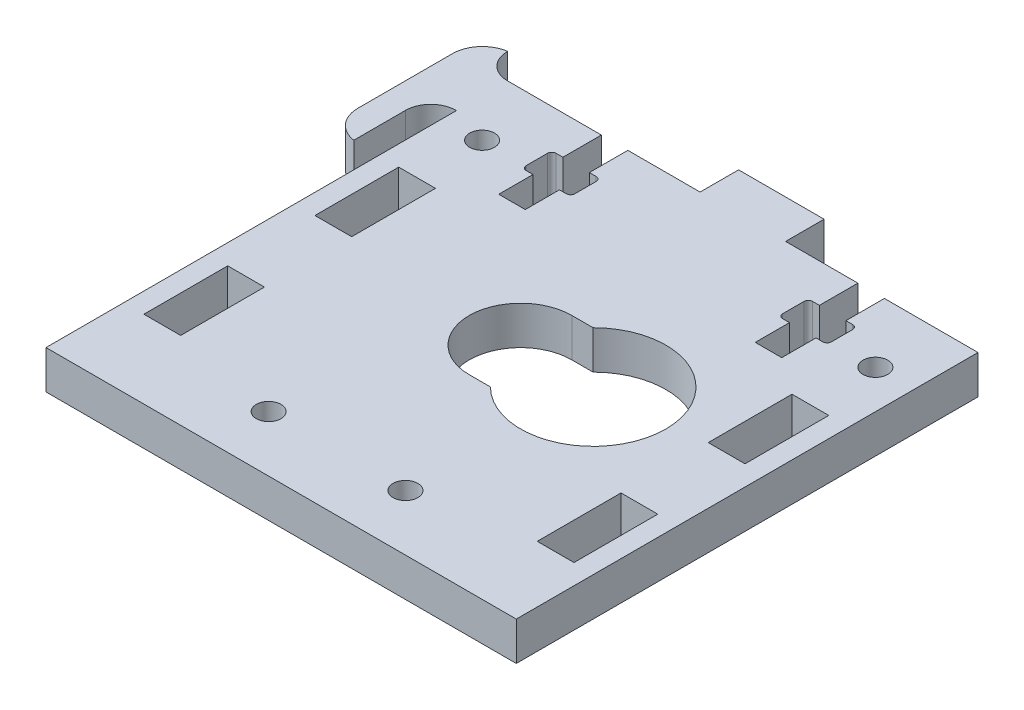
SolidWorks part; units mm, degrees
ref_plane "Front Plane" through (0, 0, 0) normal (0, 0, 1) x (1, 0, 0)
ref_plane "Top Plane" through (0, 0, 0) normal (0, 1, 0) x (1, 0, 0)
ref_plane "Right Plane" through (0, 0, 0) normal (1, 0, 0) x (0, 0, -1)
sketch "Sketch1" plane through (0, 0, 0) normal (0, 1, 0) x (1, 0, 0)
  line L1 (-27.5, 27) -> (27.5, 27)
  line L2 (-27.5, 27) -> (-27.5, -27)
  line L3 (-27.5, -27) -> (27.5, -27)
  line L4 (27.5, 27) -> (27.5, -27)
  line L5 (-27.5, 27) -> (27.5, -27) construction
  line L6 (-27.5, -27) -> (27.5, 27) construction
  point P0 (0, 0)
  dimension "D1" = 55
  dimension "D2" = 54
extrude "MainShape" add sketch "Sketch1" along normal blind 4.5
sketch "Sketch2" plane through (0, 4.5, 0) normal (0, 1, 0) x (1, 0, 0)
  line L0 (0, -27) -> (0, 27) construction
  line L1 (-27.5, -27) -> (27.5, -27) construction
  line L2 (27.5, 27) -> (-27.5, 27) construction
  line L4 (-5, 31.5) -> (5, 31.5)
  line L5 (-5, 31.5) -> (-5, 22.5)
  line L6 (-5, 22.5) -> (5, 22.5)
  line L7 (5, 31.5) -> (5, 22.5)
  line L8 (-5, 31.5) -> (5, 22.5) construction
  line L9 (-5, 22.5) -> (5, 31.5) construction
  dimension "D1" = 10
  dimension "D2" = 4.5
extrude "Tab1" add sketch "Sketch2" against normal through all
sketch "Sketch4" plane through (0, 4.5, 0) normal (0, 1, 0) x (1, 0, 0)
  line L0 (0, 31.5) -> (0, -27) construction
  line L1 (5, 31.5) -> (-5, 31.5) construction
  line L2 (-27.5, -27) -> (27.5, -27) construction
  line L3 (-15, 27) -> (-15, 15) construction
  line L4 (-5, 27) -> (-27.5, 27) construction
  line L5 (-13.45, 15) -> (-16.55, 15) construction
  line L6 (-16.55, 15) -> (-16.55, 27) construction
  line L7 (-13.45, 15) -> (-16.55, 15)
  line L8 (-16.55, 15) -> (-16.55, 19)
  line L9 (-16.55, 19) -> (-17.35, 19)
  line L10 (-17.85, 19.5) -> (-17.85, 22)
  line L11 (-17.35, 22.5) -> (-16.55, 22.5)
  line L12 (-16.55, 22.5) -> (-16.55, 27)
  line L13 (-16.55, 27) -> (-13.45, 27)
  line L14 (-13.45, 15) -> (-13.45, 27) construction
  line L15 (-13.45, 22.5) -> (-13.45, 27)
  line L16 (-12.65, 22.5) -> (-13.45, 22.5)
  line L17 (-12.15, 19.5) -> (-12.15, 22)
  line L18 (-13.45, 19) -> (-12.65, 19)
  line L19 (-13.45, 15) -> (-13.45, 19)
  line L20 (13.45, 15) -> (13.45, 27) construction
  line L21 (16.55, 15) -> (16.55, 27) construction
  line L22 (13.45, 15) -> (16.55, 15) construction
  line L23 (15, 27) -> (15, 15) construction
  line L24 (13.45, 15) -> (13.45, 19)
  line L25 (13.45, 19) -> (12.65, 19)
  line L26 (12.15, 19.5) -> (12.15, 22)
  line L27 (12.65, 22.5) -> (13.45, 22.5)
  line L28 (13.45, 22.5) -> (13.45, 27)
  line L29 (16.55, 27) -> (13.45, 27)
  line L30 (16.55, 22.5) -> (16.55, 27)
  line L31 (17.35, 22.5) -> (16.55, 22.5)
  line L32 (17.85, 19.5) -> (17.85, 22)
  line L33 (16.55, 19) -> (17.35, 19)
  line L34 (16.55, 15) -> (16.55, 19)
  line L35 (13.45, 15) -> (16.55, 15)
  arc A0 (-17.35, 19) -> (-17.85, 19.5) centre (-17.35, 19.5) cw
  arc A1 (-12.15, 19.5) -> (-12.65, 19) centre (-12.65, 19.5) cw
  arc A2 (-12.65, 22.5) -> (-12.15, 22) centre (-12.65, 22) cw
  arc A3 (-17.85, 22) -> (-17.35, 22.5) centre (-17.35, 22) cw
  arc A4 (17.85, 22) -> (17.35, 22.5) centre (17.35, 22) ccw
  arc A5 (12.65, 22.5) -> (12.15, 22) centre (12.65, 22) ccw
  arc A6 (12.15, 19.5) -> (12.65, 19) centre (12.65, 19.5) ccw
  arc A7 (17.35, 19) -> (17.85, 19.5) centre (17.35, 19.5) ccw
  point P24 (-17.85, 19)
  point P27 (-12.15, 19)
  point P30 (-12.15, 22.5)
  point P33 (-17.85, 22.5)
  point P56 (17.85, 22.5)
  point P57 (12.15, 22.5)
  point P58 (12.15, 19)
  point P59 (17.85, 19)
  dimension "D7" = 0.5
  dimension "D1" = 12
  dimension "D2" = 1.55
  dimension "D3" = 3.5
  dimension "D4" = 2.85
  dimension "D5" = 8
  dimension "D6" = 15
extrude "Cut-Extrude2" cut sketch "Sketch4" against normal through all
sketch "Sketch5" plane through (0, 4.5, 0) normal (0, 1, 0) x (1, 0, 0)
  line L0 (0, -27) -> (0, 31.5) construction
  line L1 (-27.5, -27) -> (27.5, -27) construction
  line L2 (5, 31.5) -> (-5, 31.5) construction
  line L3 (23, 27) -> (23, -27) construction
  line L4 (27.5, 27) -> (16.55, 27) construction
  line L5 (-23, 27) -> (-23, -27) construction
  line L6 (20.85, 11.9) -> (25.15, 11.9)
  line L7 (20.85, 11.9) -> (20.85, 2.1)
  line L8 (20.85, 2.1) -> (25.15, 2.1)
  line L9 (25.15, 11.9) -> (25.15, 2.1)
  line L10 (20.85, 11.9) -> (25.15, 2.1) construction
  line L11 (20.85, 2.1) -> (25.15, 11.9) construction
  line L12 (-20.85, 2.1) -> (-25.15, 11.9) construction
  line L13 (-20.85, 11.9) -> (-25.15, 2.1) construction
  line L14 (-25.15, 11.9) -> (-25.15, 2.1)
  line L15 (-20.85, 2.1) -> (-25.15, 2.1)
  line L16 (-20.85, 11.9) -> (-20.85, 2.1)
  line L17 (-20.85, 11.9) -> (-25.15, 11.9)
  line L18 (-27.5, -3) -> (27.5, -3) construction
  line L19 (-27.5, 27) -> (-27.5, -27) construction
  line L20 (27.5, -27) -> (27.5, 27) construction
  line L21 (-20.85, -17.9) -> (-25.15, -8.1) construction
  line L22 (-20.85, -8.1) -> (-25.15, -17.9) construction
  line L23 (20.85, -8.1) -> (25.15, -17.9) construction
  line L24 (20.85, -17.9) -> (25.15, -8.1) construction
  line L25 (-20.85, -17.9) -> (-25.15, -17.9)
  line L26 (-20.85, -17.9) -> (-20.85, -8.1)
  line L27 (-20.85, -8.1) -> (-25.15, -8.1)
  line L28 (-25.15, -17.9) -> (-25.15, -8.1)
  line L29 (25.15, -17.9) -> (25.15, -8.1)
  line L30 (20.85, -8.1) -> (25.15, -8.1)
  line L31 (20.85, -17.9) -> (20.85, -8.1)
  line L32 (20.85, -17.9) -> (25.15, -17.9)
  line L33 (-20.85, 11.9) -> (-25.15, 2.1) construction
  point P10 (23, 7)
  point P21 (-23, 7)
  point P36 (-23, -13)
  point P37 (23, -13)
  dimension "D1" = 23
  dimension "D2" = 9.8
  dimension "D3" = 4.3
  dimension "D4" = 20
  dimension "D5" = 20
extrude "Cut-Extrude3" cut sketch "Sketch5" against normal through all
sketch "Sketch6" plane through (0, 4.5, 0) normal (0, 1, 0) x (1, 0, 0)
  line L0 (0, -27) -> (0, 27) construction
  line L1 (5, 31.5) -> (-5, 31.5) construction
  line L3 (-27.5, 1) -> (27.5, 1) construction
  line L4 (-27.5, 27) -> (-27.5, -27) construction
  line L5 (27.5, -27) -> (27.5, 27) construction
  line L6 (27.5, 27) -> (16.55, 27) construction
  line L7 (-27.5, -27) -> (27.5, -27) construction
  line L9 (-27.5, 27) -> (27.5, 27) construction
  circle A0 centre (0, 1) radius 12
  point P4 (0, 31.5)
  dimension "D1" = 24
  dimension "D2" = 26
extrude "Cut-Extrude4" cut sketch "Sketch6" against normal through all
sketch "Sketch7" plane through (0, 4.5, 0) normal (0, 1, 0) x (1, 0, 0)
  line L0 (0, 1) -> (0, -27) construction
  line L3 (-27.5, -27) -> (27.5, -27) construction
  line L4 (8, -20.46) -> (-8, -20.46) construction
  circle A1 centre (-8, -20.46) radius 1.45
  circle A2 centre (8, -20.46) radius 1.45
  point P8 (0, -20.46)
  dimension "D1" = 2.9
  dimension "D3" = 21.46
extrude "Cut-Extrude5" [suppressed] cut sketch "Sketch7" against normal through all
sketch "Sketch8" plane through (0, 4.5, 0) normal (0, 1, 0) x (1, 0, 0)
  line L0 (-12, 1) -> (12, 1) construction
  line L1 (0, 1) -> (0, -20.46) construction
  line L2 (8, -20.46) -> (-8, -20.46) construction
  line L3 (0, -11) -> (0, 13) construction
  circle A0 centre (-8, -20.46) radius 1.45
  circle A1 centre (0, 1) radius 12 construction
  circle A2 centre (8, -20.46) radius 1.45
  dimension "D3" = 2.9
  dimension "D1" = 90
  dimension "D4" = 21.46
extrude "Cut-Extrude6" cut sketch "Sketch8" against normal through all
sketch "Sketch9" plane through (0, 4.5, 0) normal (0, 1, 0) x (1, 0, 0)
  line L0 (0, -27) -> (0, 31.5) construction
  line L1 (-27.5, -27) -> (27.5, -27) construction
  line L2 (5, 31.5) -> (-5, 31.5) construction
  line L3 (16, -27) -> (16, -16) construction
  line L4 (14.45, -16) -> (17.55, -16) construction
  line L5 (17.55, -16) -> (17.55, -27) construction
  line L6 (17.55, -27) -> (17.55, -22.5)
  line L7 (17.55, -22.5) -> (18.35, -22.5)
  line L8 (18.85, -22) -> (18.85, -19.5)
  line L9 (18.35, -19) -> (17.55, -19)
  line L10 (17.55, -19) -> (17.55, -16)
  line L11 (17.55, -16) -> (14.45, -16)
  line L12 (17.55, -27) -> (14.45, -27)
  line L13 (14.45, -16) -> (14.45, -27) construction
  line L14 (14.45, -19) -> (14.45, -16)
  line L15 (13.65, -19) -> (14.45, -19)
  line L16 (13.15, -22) -> (13.15, -19.5)
  line L17 (14.45, -22.5) -> (13.65, -22.5)
  line L18 (14.45, -27) -> (14.45, -22.5)
  line L19 (-14.45, -16) -> (-14.45, -27) construction
  line L20 (-17.55, -16) -> (-17.55, -27) construction
  line L21 (-14.45, -16) -> (-17.55, -16) construction
  line L22 (-16, -27) -> (-16, -16) construction
  line L23 (-14.45, -27) -> (-14.45, -22.5)
  line L24 (-14.45, -22.5) -> (-13.65, -22.5)
  line L25 (-13.15, -22) -> (-13.15, -19.5)
  line L26 (-13.65, -19) -> (-14.45, -19)
  line L27 (-14.45, -19) -> (-14.45, -16)
  line L28 (-17.55, -27) -> (-14.45, -27)
  line L29 (-17.55, -16) -> (-14.45, -16)
  line L30 (-17.55, -19) -> (-17.55, -16)
  line L31 (-18.35, -19) -> (-17.55, -19)
  line L32 (-18.85, -22) -> (-18.85, -19.5)
  line L33 (-17.55, -22.5) -> (-18.35, -22.5)
  line L34 (-17.55, -27) -> (-17.55, -22.5)
  arc A0 (18.35, -22.5) -> (18.85, -22) centre (18.35, -22) ccw
  arc A1 (18.85, -19.5) -> (18.35, -19) centre (18.35, -19.5) ccw
  arc A2 (13.15, -19.5) -> (13.65, -19) centre (13.65, -19.5) cw
  arc A3 (13.65, -22.5) -> (13.15, -22) centre (13.65, -22) cw
  arc A4 (-13.65, -22.5) -> (-13.15, -22) centre (-13.65, -22) ccw
  arc A5 (-13.15, -19.5) -> (-13.65, -19) centre (-13.65, -19.5) ccw
  arc A6 (-18.85, -19.5) -> (-18.35, -19) centre (-18.35, -19.5) cw
  arc A7 (-18.35, -22.5) -> (-18.85, -22) centre (-18.35, -22) cw
  point P16 (18.85, -22.5)
  point P19 (18.85, -19)
  point P30 (13.15, -19)
  point P31 (13.15, -22.5)
  point P54 (-13.15, -22.5)
  point P55 (-13.15, -19)
  point P56 (-18.85, -19)
  point P57 (-18.85, -22.5)
  dimension "D7" = 0.5
  dimension "D2" = 1.55
  dimension "D1" = 11
  dimension "D3" = 8
  dimension "D4" = 3.5
  dimension "D5" = 2.85
  dimension "D6" = 16
extrude "Cut-Extrude7" [suppressed] cut sketch "Sketch9" against normal through all
sketch "Sketch10" [suppressed] plane through (0, 0, 27) normal (0, 0, 1) x (1, 0, 0)
  line L0 (-27.5, 2.25) -> (27.5, 2.25) construction
  line L1 (-27.5, 4.5) -> (-27.5, 0) construction
  line L2 (27.5, 4.5) -> (27.5, 0) construction
  line L3 (-16, 4.5) -> (-16, 0) construction
  line L4 (-14.25, 4.5) -> (-17.75, 4.5) construction
  line L5 (16, 4.5) -> (16, 0) construction
  line L6 (17.75, 4.5) -> (14.25, 4.5) construction
  line L7 (17.75, 0) -> (14.25, 0) construction
  line L8 (-14.25, 0) -> (-17.75, 0) construction
  circle A0 centre (-16, 2.25) radius 1.6
  circle A1 centre (16, 2.25) radius 1.6
  dimension "D1" = 3.2
  dimension "D2" = 3.2
sketch "Sketch11" plane through (0, 4.5, 0) normal (0, 1, 0) x (1, 0, 0)
  line L0 (-20.85, 7) -> (-25.15, 7) construction
  line L1 (-20.85, 2.1) -> (-20.85, 11.9) construction
  line L2 (-25.15, 11.9) -> (-25.15, 2.1) construction
  line L3 (-23, 7) -> (-23, 27) construction
  line L4 (-16.55, 27) -> (-27.5, 27) construction
  line L5 (0, 31.5) -> (0, 0) construction
  line L6 (5, 31.5) -> (-5, 31.5) construction
  line L7 (23, 7) -> (23, 27) construction
  line L8 (20.85, 7) -> (25.15, 7) construction
  line L9 (-23, 7) -> (-23, 27) construction
  circle A0 centre (-23, 19.5) radius 1.45
  circle A1 centre (23, 19.5) radius 1.45
  dimension "D1" = 2.9
  dimension "D2" = 7.5
extrude "Cut-Extrude8" cut sketch "Sketch11" against normal through all
sketch "Sketch12" [suppressed] plane through (0, 4.5, 0) normal (0, 1, 0) x (1, 0, 0)
  line L0 (-27.5, -7) -> (-34, -17)
  line L1 (-27.5, 27) -> (-27.5, -27) construction
  line L2 (-34, -17) -> (-34, -27)
  line L3 (-34, -27) -> (-27.5, -27)
  line L4 (-27.5, -27) -> (-27.5, -7)
  line L5 (-27.5, -27) -> (27.5, -27) construction
  line L6 (0, -27) -> (0, 31.5) construction
  line L7 (5, 31.5) -> (-5, 31.5) construction
  line L8 (27.5, -27) -> (27.5, -7)
  line L9 (34, -27) -> (27.5, -27)
  line L10 (34, -17) -> (34, -27)
  line L11 (27.5, -7) -> (34, -17)
  point P4 (0, -27)
  dimension "D1" = 34
  dimension "D2" = 10
  dimension "D3" = 20
extrude "Boss-Extrude1" [suppressed] add sketch "Sketch12" against normal through all
sketch "Sketch14" [suppressed] plane through (0, 4.5, 0) normal (0, 1, 0) x (1, 0, 0)
  line L0 (-34, -27) -> (34, -27) construction
  line L2 (-34, -27) -> (34, -27) construction
  line L3 (0, -27) -> (0, 31.5) construction
  line L4 (5, 31.5) -> (-5, 31.5) construction
  line L6 (26.25, -16.5) -> (26.25, -27) construction
  line L8 (-28, -27) -> (-28, -16.5) construction
  line L9 (-26.25, -16.5) -> (-29.75, -16.5) construction
  line L10 (-29.75, -16.5) -> (-29.75, -27) construction
  line L11 (-26.25, -27) -> (-29.75, -27)
  line L12 (-29.75, -27) -> (-29.75, -23.2)
  line L13 (-29.75, -23.2) -> (-30.75, -23.2)
  line L14 (-31, -22.95) -> (-31, -19.25)
  line L15 (-30.75, -19) -> (-29.75, -19)
  line L16 (-29.75, -19) -> (-29.75, -16.5)
  line L17 (-29.75, -16.5) -> (-26.25, -16.5)
  line L18 (-26.25, -16.5) -> (-26.25, -27) construction
  line L19 (-26.25, -19) -> (-26.25, -16.5)
  line L20 (-25.25, -19) -> (-26.25, -19)
  line L21 (-25, -22.95) -> (-25, -19.25)
  line L22 (-26.25, -23.2) -> (-25.25, -23.2)
  line L23 (-26.25, -27) -> (-26.25, -23.2)
  line L24 (29.75, -16.5) -> (29.75, -27) construction
  line L25 (26.25, -16.5) -> (29.75, -16.5) construction
  line L26 (28, -27) -> (28, -16.5) construction
  line L27 (26.25, -27) -> (26.25, -23.2)
  line L28 (26.25, -23.2) -> (25.25, -23.2)
  line L29 (25, -22.95) -> (25, -19.25)
  line L30 (25.25, -19) -> (26.25, -19)
  line L31 (26.25, -19) -> (26.25, -16.5)
  line L32 (29.75, -16.5) -> (26.25, -16.5)
  line L33 (29.75, -19) -> (29.75, -16.5)
  line L34 (30.75, -19) -> (29.75, -19)
  line L35 (31, -22.95) -> (31, -19.25)
  line L36 (29.75, -23.2) -> (30.75, -23.2)
  line L37 (29.75, -27) -> (29.75, -23.2)
  line L38 (26.25, -27) -> (29.75, -27)
  line L39 (-26.25, -16.5) -> (-26.25, -27) construction
  arc A0 (-30.75, -23.2) -> (-31, -22.95) centre (-30.75, -22.95) cw
  arc A1 (-31, -19.25) -> (-30.75, -19) centre (-30.75, -19.25) cw
  arc A2 (-25, -19.25) -> (-25.25, -19) centre (-25.25, -19.25) ccw
  arc A3 (-25.25, -23.2) -> (-25, -22.95) centre (-25.25, -22.95) ccw
  arc A4 (25.25, -23.2) -> (25, -22.95) centre (25.25, -22.95) cw
  arc A5 (25, -19.25) -> (25.25, -19) centre (25.25, -19.25) cw
  arc A6 (31, -19.25) -> (30.75, -19) centre (30.75, -19.25) ccw
  arc A7 (30.75, -23.2) -> (31, -22.95) centre (30.75, -22.95) ccw
  point P2 (0, -27)
  dimension "D10" = 0.5
  dimension "D4" = 1.55
  dimension "D6" = 11
  dimension "D2" = 28
  dimension "D3" = 2.85
  dimension "D5" = 3.5
  dimension "D7" = 8
extrude "Cut-Extrude9" [suppressed] cut sketch "Sketch14" against normal through all
sketch "Sketch15" plane through (0, 4.5, 0) normal (0, 1, 0) x (1, 0, 0)
  circle A0 centre (0, 1) radius 12
  circle A1 centre (0, 1) radius 6
  circle A2 centre (0, 1) radius 12 construction
  dimension "D1" = 12
extrude "Boss-Extrude2" add sketch "Sketch15" against normal through all
sketch "Sketch16" plane through (0, 4.5, 0) normal (0, 1, 0) x (1, 0, 0)
  line L0 (0, 1) -> (27.5, 1) construction
  line L1 (27.5, -27) -> (27.5, 27) construction
  line L2 (0, 7) -> (2.4792, 7)
  line L3 (0, -5) -> (2.4792, -5)
  line L4 (0, 7) -> (0, -5)
  arc A0 (2.4792, -5) -> (2.4792, 7) centre (8.5, 1) ccw
  circle A1 centre (0, 1) radius 6 construction
  dimension "D1" = 17
  dimension "D2" = 8.5
extrude "Cut-Extrude10" cut sketch "Sketch16" against normal through all
sketch "Sketch17" plane through (0, 4.5, 0) normal (0, 1, 0) x (1, 0, 0)
  line L0 (-27.5, 22) -> (-27.5, 18) construction
  line L1 (-27.5, 27) -> (-27.5, -27) construction
  line L2 (-27.5, 25.5) -> (-27.5, 23.5)
  line L3 (-29, 22) -> (-29, 18)
  line L4 (-27.5, 22) -> (-27.5, 18) construction
  line L5 (-27.5, 16.5) -> (-27.5, 14.5)
  line L6 (-31, 22) -> (-31, 18)
  line L7 (-27.5, 25.5) -> (-27.5, 14.5) construction
  arc A0 (-27.5, 23.5) -> (-29, 22) centre (-27.5, 22) ccw
  arc A1 (-29, 18) -> (-27.5, 16.5) centre (-27.5, 18) ccw
  arc A2 (-27.5, 25.5) -> (-31, 22) centre (-27.5, 22) ccw
  arc A3 (-31, 18) -> (-27.5, 14.5) centre (-27.5, 18) ccw
  point P10 (-27.5, 20)
  dimension "D1" = 1.5
  dimension "D2" = 1.5
  dimension "D3" = 2
  dimension "D4" = 4
  dimension "D5" = 20
  dimension "D7" = 2
extrude "CableTieSlot" [suppressed] add sketch "Sketch17" against normal through all
sketch "Sketch18" plane through (0, 4.5, 0) normal (0, 1, 0) x (1, 0, 0)
  line L0 (-27.5, 27) -> (-27.55, 27)
  line L1 (-33.5, 30) -> (-33.5, 12)
  line L2 (-33.5, 12) -> (-30.5, 12)
  line L3 (-30.5, 12) -> (-30.5, 18.05)
  line L4 (-27.55, 21) -> (-27.5, 21)
  line L5 (-27.5, 27) -> (-27.5, -27) construction
  line L6 (-27.5, 21) -> (-27.5, 27)
  line L7 (-16.55, 27) -> (-27.5, 27) construction
  line L8 (-33.5, 30) -> (-30.5, 30)
  line L9 (-30.5, 30) -> (-30.5, 29.95)
  arc A0 (-27.55, 27) -> (-30.5, 29.95) centre (-27.55, 29.95) cw
  arc A1 (-30.5, 18.05) -> (-27.55, 21) centre (-27.55, 18.05) cw
  point P17 (-30.5, 27)
  dimension "D1" = 2.95
  dimension "D2" = 2.95
  dimension "D3" = 6
  dimension "D4" = 3
  dimension "D5" = 15
  dimension "D6" = 3
  dimension "D7" = 3
extrude "Boss-Extrude3" add sketch "Sketch18" against normal through all
fillet "Fillet1" radius 3.5 2 edges at (-33.5, 2.25, -30) (-33.5, 2.25, -12)
equation "\"X-ROD-SPACING\"=45"
equation "\"Y-ROD-SPACING\"=75"
equation "\"Z-ROD-SPACING\"=17.5"
equation "\"Y-BED-OFFSET\"=2"
equation "\"Y-BED-ROD-INSET\"=3.5"
equation "\"Y-BED-SCREW-SPACING\"=209"
equation "\"Y-BED-SCREW-CUTOUT-SLOT-HEIGHT\"=2"
equation "\"T-SLOT-NUT-FILLET-RADIUS\"=0.5"
equation "\"T-SLOT-SCREW-SHAFT-RADIUS\"=1.55"
equation "\"T-SLOT-SCREW-SHAFT-CUTOUT-LENGTH\"=11"
equation "\"T-SLOT-NUT-DEPTH\"=3.5"
equation "\"T-SLOT-NUT-WIDTH\"=2.85"
equation "\"T-SLOT-NUT-END-DISTANCE\"=8"
equation "\"ACRYLIC-THICKNESS\"=10"
equation "\"ACRYLIC-THICKNESS2\"=4.5"
equation "\"ACRYLIC-TAB-CUTOUT-SIZE\"=\"ACRYLIC-THICKNESS\"+\"ACRYLIC-TAB-TOLERANCE\"*2"
equation "\"ACRYLIC-TAB-WIDTH\"=\"ACRYLIC-THICKNESS\""
equation "\"ACRYLIC-M3-HOLE\"=2.9"
equation "\"SMOOTHROD-CAP-SCREW-DISTANCE\"=20"
equation "\"FRAME-WIDTH-INNER\"=370"
equation "\"NEMA17-HOLE-SPACING\"=31"
equation "\"NEMA17-CENTRAL-CUTOUT\"=22.5"
equation "\"Z-BRACKET-REACH\"=55"
equation "\"Z-ROD-INSET\"=13.5"
equation "\"TOP-BRACKET-SPACING\"=40"
equation "\"SMOOTHROD-X-LENGTH\"=350"
equation "\"SMOOTHROD-Y-LENGTH\"=350"
equation "\"SMOOTHROD-Z-LENGTH\"=350"
equation "\"SMOOTHROD-TIGHTENING-HEADROOM\"=.25"
equation "\"LEADSCREW-Z-LENGTH\"=300"
equation "\"SCREW-LENGTH-FRAME\"=\"ACRYLIC-THICKNESS\" + 10"
equation "\"SCREW-LENGTH-MOTOR\"=\"ACRYLIC-THICKNESS\" + 5"
equation "\"SCREW-LENGTH-EXTRUDER\"=28"
equation "\"SCREW-HEAD-RADIUS\"=6"
equation "\"PRINTED-X-SMOOTHROD-DIAMETER\"=9.0"
equation "\"PRINTED-X-SMOOTHROD-CUTOUT\"=10"
equation "\"PRINTED-X-BASE-HEIGHT\"=10"
equation "\"PRINTED-LM8UU-CUTOUT-SIZE\"=15.5"
equation "\"PRINTED-LM8UU-CUTOUT-LENGTH\"=24.5"
equation "\"PRINTED-X-IDLER-HEIGHT\"=16"
equation "\"PSU-MOUNTING-WIDTH\"=95"
equation "\"PSU-MOUNTING-HEIGHT\"=177"
equation "\"Y-BELT-TO-ROD-DISTANCE\"=20"
equation "\"SPOOL-HOLDER-ROD-SPACING\"=150"
equation "\"ACRYLIC-X-CARRIAGE-WIDTH\"=55"
equation "\"ACRYLIC-X-CARRIAGE-HEIGHT\"=75"
equation "\"ACRYLIC-X-CARRIAGE-SCREW-SPACING-X\"=15"
equation "\"ACRYLIC-X-CARRIAGE-SCREW-SPACING-Y\"=33"
equation "\"ACRYLIC-X-CARRIAGE-CENTER-TAB-SPACING\"=14"
equation "\"D1@Sketch1\"=\"ACRYLIC-X-CARRIAGE-WIDTH\""
equation "\"D1@MainShape\" = \"ACRYLIC-THICKNESS2\""
equation "\"D1@Sketch2\"=\"ACRYLIC-TAB-WIDTH\""
equation "\"D2@Sketch2\"=\"ACRYLIC-THICKNESS2\""
equation "\"D1@Sketch4\"=\"T-SLOT-SCREW-SHAFT-CUTOUT-LENGTH\"+1"
equation "\"D2@Sketch4\"=\"T-SLOT-SCREW-SHAFT-RADIUS\""
equation "\"D3@Sketch4\"=\"T-SLOT-NUT-DEPTH\""
equation "\"D4@Sketch4\"=\"T-SLOT-NUT-WIDTH\""
equation "\"D5@Sketch4\"=\"T-SLOT-NUT-END-DISTANCE\""
equation "\"D6@Sketch4\"=\"ACRYLIC-X-CARRIAGE-SCREW-SPACING-X\""
equation "\"D7@Sketch4\"=\"T-SLOT-NUT-FILLET-RADIUS\""
equation "\"ACRYLIC-X-CARRIAGE-EXTRUDER-SHELF-DEPTH\"=\"ACRYLIC-X-CARRIAGE-EXTRUDER-OFFSET\" + 28"
equation "\"D2@Sketch1\"=\"ACRYLIC-X-CARRIAGE-EXTRUDER-SHELF-DEPTH\""
equation "\"ACRYLIC-X-CARRIAGE-LM8UU-CUTOUT-WIDTH\"=24.25"
equation "\"ACRYLIC-X-CARRIAGE-EXTRUDER-BRACE-SPACING\"=23"
equation "\"ACRYLIC-X-CARRIAGE-EXTRUDER-BRACE-TAB-OFFSET\"=20"
equation "\"ACRYLIC-X-CARRIAGE-EXTRUDER-BRACE-HEIGHT\"=35"
equation "\"ACRYLIC-X-CARRIAGE-EXTRUDER-BRACE-SCREW-SPACING\"=22"
equation "\"D1@Sketch5\"=\"ACRYLIC-X-CARRIAGE-EXTRUDER-BRACE-SPACING\""
equation "\"D2@Sketch5\"=\"ACRYLIC-TAB-WIDTH\"-\"KERF\"*2"
equation "\"D3@Sketch5\"=\"ACRYLIC-THICKNESS2\"-\"KERF\"*2"
equation "\"D4@Sketch5\"=\"ACRYLIC-X-CARRIAGE-EXTRUDER-BRACE-TAB-OFFSET\""
equation "\"D1@Sketch7\"=\"ACRYLIC-M3-HOLE\""
equation "\"D3@Sketch8\"=\"ACRYLIC-M3-HOLE\""
equation "\"ACRYLIC-X-CARRIAGE-EXTRUDER-ANGLE\"=90"
equation "\"D1@Sketch8\"=\"ACRYLIC-X-CARRIAGE-EXTRUDER-ANGLE\""
equation "\"ACRYLIC-X-CARRIAGE-EXTRUDER-OFFSET\"=26"
equation "\"D2@Sketch6\"=\"ACRYLIC-X-CARRIAGE-EXTRUDER-OFFSET\""
equation "\"D1@Sketch9\"=\"T-SLOT-SCREW-SHAFT-CUTOUT-LENGTH\""
equation "\"D2@Sketch9\"=\"T-SLOT-SCREW-SHAFT-RADIUS\""
equation "\"D3@Sketch9\"=\"T-SLOT-NUT-END-DISTANCE\""
equation "\"D4@Sketch9\"=\"T-SLOT-NUT-DEPTH\""
equation "\"D5@Sketch9\"=\"T-SLOT-NUT-WIDTH\""
equation "\"D7@Sketch9\"=\"T-SLOT-NUT-FILLET-RADIUS\""
equation "\"ACRYLIC-TAB-TOLERANCE\"=-.05"
equation "\"D1@Sketch11\"=\"ACRYLIC-M3-HOLE\""
equation "\"D6@Sketch14\"=\"T-SLOT-SCREW-SHAFT-CUTOUT-LENGTH\""
equation "\"D3@Sketch14\"=\"T-SLOT-NUT-WIDTH\""
equation "\"D5@Sketch14\"=\"T-SLOT-NUT-DEPTH\""
equation "\"D4@Sketch14\"=\"T-SLOT-SCREW-SHAFT-RADIUS\""
equation "\"D10@Sketch14\"=\"T-SLOT-NUT-FILLET-RADIUS\""
equation "\"D7@Sketch14\"=\"T-SLOT-NUT-END-DISTANCE\""
equation "\"KERF\"=0.1"
equation "\"PRINTED-M3-HOLE\"=3.5"
equation "\"PRINTED-M3-NUT-AF\"=6.25"
equation "\"ACRYLIC-X-CARRIAGE-LM8UU-CUTOUT-HEIGHT\"=11.0"
equation "\"ACRYLIC-X-CARRIAGE-DUAL-WIDTH-MULTIPLIER\"=1.65"
equation "\"ACRYLIC-X-CARRIAGE-DUAL-HOTEND-SPACING\"=42"
equation "\"ACRYLIC-X-CARRIAGE-DUAL-WIDTH\"=75"
equation "\"ACRYLIC-X-CARRIAGE-DUAL-FAN-OFFSET\"=52"
equation "\"ACRYLIC-X-CARRIAGE-DUAL-FAN-HEIGHT\"=20"
equation "\"ACRYLIC-X-CARRIAGE-DUAL-HOTEND-SEPARATION\"=36"
equation "\"ACRYLIC-X-CARRIAGE-DUAL-MOUNT-PLATE-DEPTH\"=75"
equation "\"ACRYLIC-X-CARRIAGE-DUAL-MOUNT-BRACE-WIDTH\"=33"
equation "\"ACRYLIC-X-CARRIAGE-DUAL-MOUNT-SCREW-WIDTH\"=40"
equation "\"BLOWER-FAN-WIDTH\"=15"
